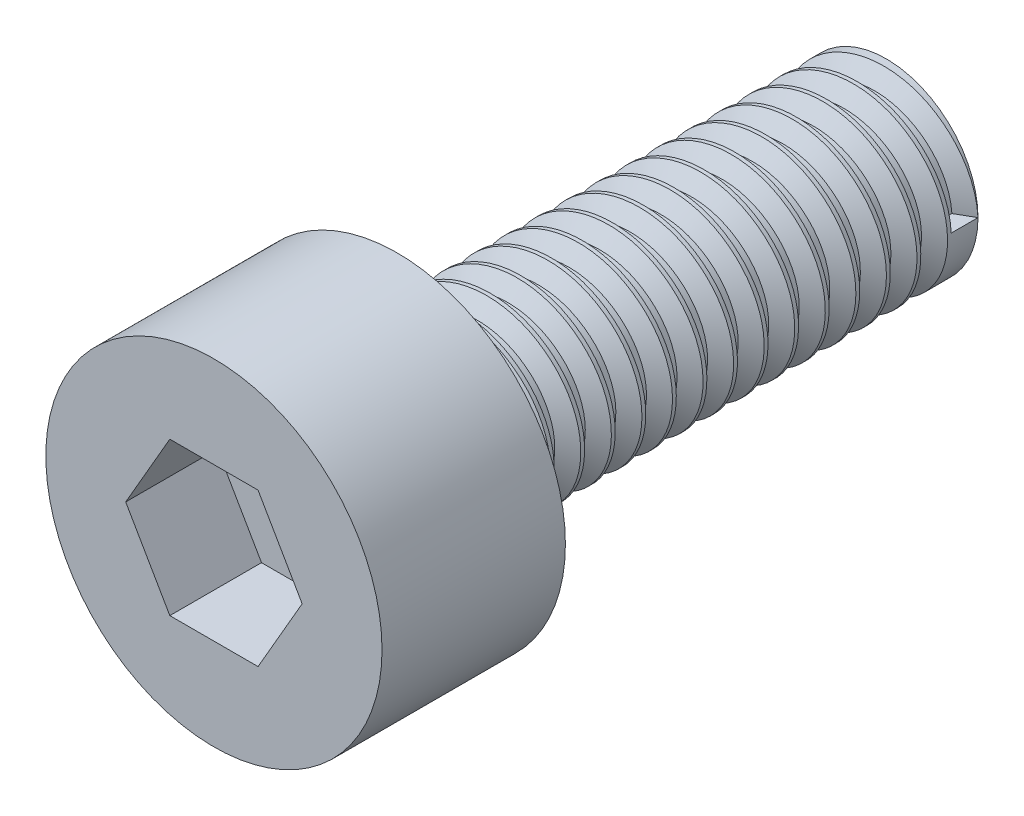
SolidWorks part; units mm, degrees
ref_plane "前视基准面" through (0, 0, 0) normal (0, 0, 1) x (1, 0, 0)
ref_plane "上视基准面" through (0, 0, 0) normal (0, 1, 0) x (1, 0, 0)
ref_plane "右视基准面" through (0, 0, 0) normal (1, 0, 0) x (0, 0, -1)
sketch "草图1" plane through (0, 0, 0) normal (0, 0, 1) x (1, 0, 0)
  circle A0 centre (0, 0) radius 1.5
  dimension "diameter" = 3
extrude "螺杆_直径3_长度10" add sketch "草图1" along normal blind 8
thread "真实螺纹_M3x0.5_右旋_长10" pitch 0.5 method cut profile "螺纹线轮廓1" start angle 0, offset 0, length 8, pitch 0.5, diameter 3
ref_plane "基准面4" through (1.5, 0, 0) normal (0, -1, 0) x (1, 0, 0)
sketch "螺纹线轮廓1" plane through (1.5, 0, 0) normal (0, -1, 0) x (1, 0, 0)
  line L0 (0, 0) -> (0, 0.5) construction
  line L11 (0, 0) -> (0, 0.4375)
  line L12 (0, 0.4375) -> (-0.2706, 0.2812)
  line L13 (-0.2706, 0.2812) -> (-0.2706, 0.1562)
  line L15 (-0.2706, 0.1562) -> (0, 0)
  line L17 (-0.2706, 0.2187) -> (0, 0.2187) construction
  point P2 (0, 0)
  dimension "Pitch" = 0.5
  dimension "Profile_Angle" = 60
  dimension "Profile_Land" = 0.125
  dimension "Profile_Height" = 0.2706
sketch "草图2" plane through (0, 0, 8) normal (0, 0, 1) x (1, 0, 0)
  circle A0 centre (0, 0) radius 2.75
  dimension "diameter" = 5.5
extrude "杯头_直径5.5_厚度3" add sketch "草图2" along normal blind 3
sketch "草图3" plane through (0, 0, 11) normal (0, 0, 1) x (1, 0, 0)
  line L0 (1.4434, 0) -> (0.7217, 1.25)
  line L1 (0.7217, 1.25) -> (-0.7217, 1.25)
  line L2 (-0.7217, 1.25) -> (-1.4434, 0)
  line L3 (-1.4434, 0) -> (-0.7217, -1.25)
  line L4 (-0.7217, -1.25) -> (0.7217, -1.25)
  line L5 (0.7217, -1.25) -> (1.4434, 0)
  dimension "x0" = 1.4434
  dimension "x1" = 0.7217
  dimension "x2" = 0.7217
  dimension "x3" = 1.4434
  dimension "x4" = 0.7217
  dimension "x5" = 0.7217
  dimension "y1" = 1.25
  dimension "y4" = 1.25
extrude "内六角_对边2.5_深1.5" cut sketch "草图3" against normal blind 1.5
